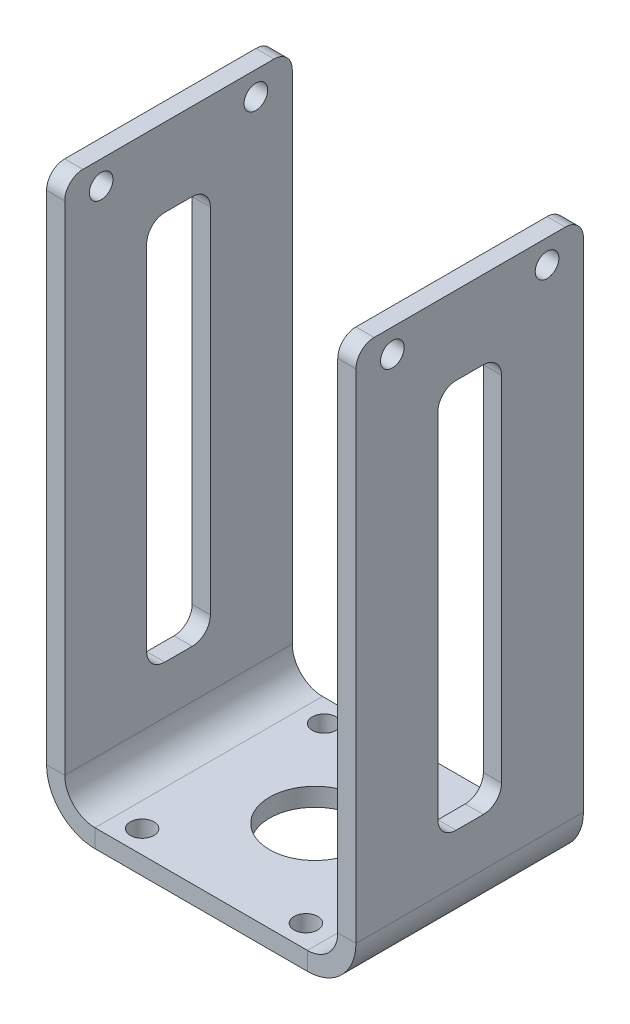
SolidWorks part; units mm, degrees
note: The reader was unsure of these and kept them because the rebuilt part matched: bend radius of "Base-Flange1", "BaseBend1", "BaseBend2".
material "2024 Alloy (SN)"
ref_plane "Front Plane" through (0, 0, 0) normal (0, 0, 1) x (1, 0, 0)
ref_plane "Top Plane" through (0, 0, 0) normal (0, 1, 0) x (1, 0, 0)
ref_plane "Right Plane" through (0, 0, 0) normal (1, 0, 0) x (0, 0, -1)
sketch "Sketch1" plane through (0, 0, 0) normal (0, 0, 1) x (1, 0, 0)
  line L0 (-15, 60) -> (-15, 0)
  line L1 (-15, 0) -> (15, 0)
  line L2 (15, 0) -> (15, 60)
  point P2 (0, 0)
  dimension "D1" = 60
  dimension "D2" = 30
sheet metal parameters "Sheet-Metal1" thickness 2 parameters "D1"=3.33
base flange "Base-Flange1" sketch "Sketch1" end condition mid plane depth 25 reverse direction no thickness 2 reverse thickness direction no bend radius 3.33
bend "BaseBend1" bend radius 3.33 bend angle 90 parameters "D5"=1
bend "BaseBend2" bend radius 3.33 bend angle 90 parameters "D5"=2
sketch "Sketch7" plane through (0, 0, 0) normal (1, 0, 0) x (0, 0, -1)
  line L3 (-12.5, 60) -> (12.5, 60) construction
  circle A0 centre (-8.5, 57.4) radius 1.3
  circle A2 centre (8.5, 57.4) radius 1.3
  dimension "D1" = 17
  dimension "D2" = 8.5
  dimension "D3" = 2.6
  dimension "D6" = 2.6
extrude "Cut-Extrude2" cut sketch "Sketch7" against normal through all and the other way through all normal cut yes
sketch "Sketch16" plane through (0, -2, 0) normal (0, -1, 0) x (1, 0, 0)
  circle A0 centre (0, 0) radius 5
  point P0 (0, 0)
  dimension "D1" = 10
extrude "Cut-Extrude5" cut sketch "Sketch16" against normal blind 10 normal cut yes
sketch "Sketch17" plane through (0, 0, 0) normal (0, 1, 0) x (1, 0, 0)
  line L1 (-9, 10) -> (9, 10) construction
  line L2 (-9, 10) -> (-9, -10) construction
  line L3 (-9, -10) -> (9, -10) construction
  line L4 (9, 10) -> (9, -10) construction
  line L5 (-9, 10) -> (9, -10) construction
  line L6 (-9, -10) -> (9, 10) construction
  circle A0 centre (-9, 10) radius 1.3
  circle A1 centre (9, 10) radius 1.3
  circle A2 centre (9, -10) radius 1.3
  circle A3 centre (-9, -10) radius 1.3
  point P8 (0, 0)
  dimension "D1" = 20
  dimension "D3" = 2.6
  dimension "D2" = 18
extrude "Cut-Extrude6" cut sketch "Sketch17" against normal blind 10 normal cut yes
fillet "Fillet3" radius 2 4 edges at (16, 60, -12.5) (16, 60, 12.5) (-16, 60, 12.5) (-16, 60, -12.5)
sketch "Sketch18" plane through (-17, 0, 0) normal (-1, 0, 0) x (0, 0, 1)
  line L0 (0, 0) -> (0, 60) construction
  line L1 (-3.5, 51.4) -> (3.5, 51.4)
  line L2 (-3.5, 51.4) -> (-3.5, 8.6)
  line L3 (-3.5, 8.6) -> (3.5, 8.6)
  line L4 (3.5, 51.4) -> (3.5, 8.6)
  line L5 (-3.5, 51.4) -> (3.5, 8.6) construction
  line L6 (-3.5, 8.6) -> (3.5, 51.4) construction
  line L7 (-12.5, 58) -> (-12.5, 3.33) construction
  circle A0 centre (-8.5, 57.4) radius 1.3 construction
  point P0 (0, 30)
  dimension "D1" = 6
  dimension "D2" = 9
extrude "Cut-Extrude7" cut sketch "Sketch18" against normal through all normal cut yes
fillet "Fillet4" radius 2 8 edges at (16, 8.6, 3.5) (16, 51.4, 3.5) (16, 51.4, -3.5) (16, 8.6, -3.5) (-16, 8.6, -3.5) (-16, 8.6, 3.5) (-16, 51.4, 3.5) (-16, 51.4, -3.5)
flat pattern "Flat-Pattern1" [suppressed]
sketch "Bend-Lines1" plane through (0, 0, 0) normal (0, 1, 0) x (-1, 0, 0)
  line L0 (16.0708, 12.5) -> (16.0708, -12.5) construction
  line L1 (-16.0708, -12.5) -> (-16.0708, 12.5) construction
  line L2 (16.0708, 12.5) -> (16.0708, -12.5) construction
  line L3 (-16.0708, -12.5) -> (-16.0708, 12.5) construction
sketch3d "Bounding-Box1" [suppressed]
  line L0 (60.1415, -0.0001, 0) -> (-92.1415, 0, 0) construction
  line L1 (60.1415, -25, 0) -> (-92.1416, -24.9999, 0) construction
  line L2 (60.1415, -0.0001, 0) -> (60.1415, -25, 0) construction
  line L3 (-92.1415, 0, 0) -> (-92.1416, -24.9999, 0) construction
bend of the flat pattern "Flatten-<BaseBend1>1"
bend of the flat pattern "Flatten-<BaseBend2>1"
